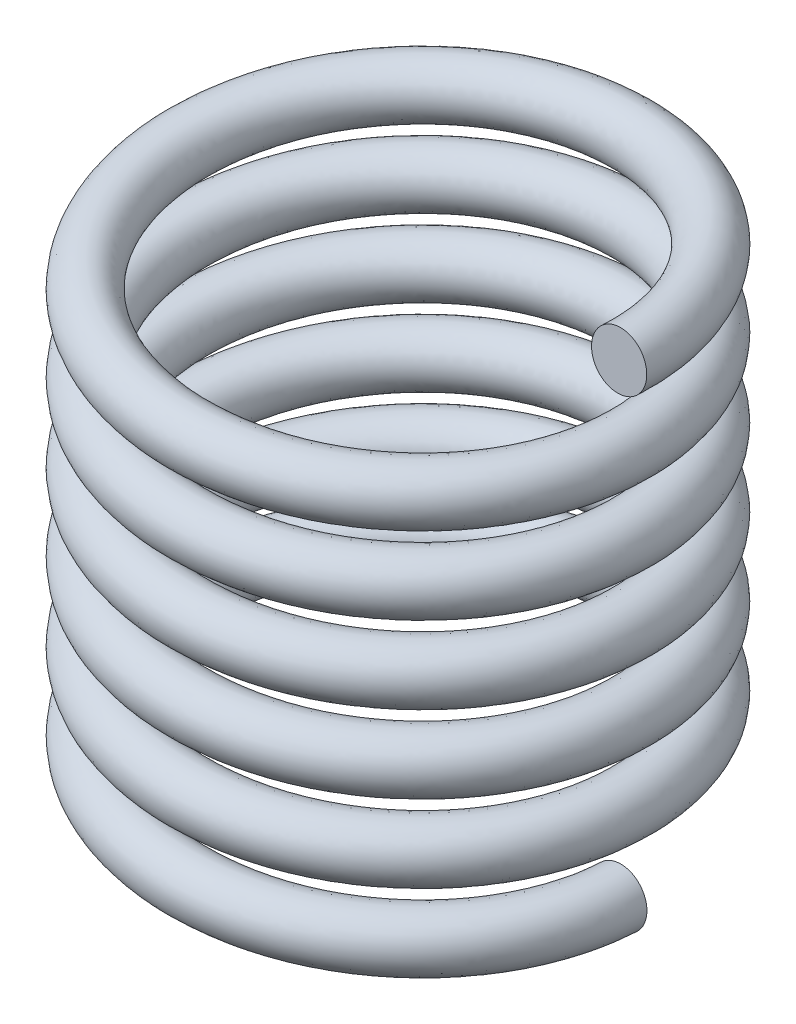
SolidWorks part; units mm, degrees
ref_plane "前视基准面" through (0, 0, 0) normal (0, 0, 1) x (1, 0, 0)
ref_plane "上视基准面" through (0, 0, 0) normal (0, 1, 0) x (1, 0, 0)
ref_plane "右视基准面" through (0, 0, 0) normal (1, 0, 0) x (0, 0, -1)
other "Configuration Table"
sketch3d "3D草图1"
  spline S0 degree 3 poles (10, 0, 0) (10.0054, 0.0972, 1.7467) (9.296, 0.2431, 4.3593) (7.1522, 0.4375, 7.1523) (5.0575, 0.5833, 8.7598) (2.6179, 0.7292, 9.7702) (0, 0.875, 10.1149) (-2.6179, 1.0208, 9.7702) (-5.0574, 1.1667, 8.7597) (-7.1523, 1.3125, 7.1523) (-8.7597, 1.4583, 5.0574) (-9.7702, 1.6042, 2.6179) (-10.1149, 1.75, 0) (-9.7702, 1.8958, -2.6179) (-8.7597, 2.0417, -5.0574) (-7.1523, 2.1875, -7.1523) (-5.0574, 2.3333, -8.7597) (-2.6179, 2.4792, -9.7702) (0, 2.625, -10.1149) (2.6179, 2.7708, -9.7702) (5.0574, 2.9167, -8.7597) (7.1523, 3.0625, -7.1523) (8.7597, 3.2083, -5.0574) (9.7702, 3.3542, -2.6179) (10.1149, 3.5, 0) (9.7702, 3.6458, 2.6179) (8.7597, 3.7917, 5.0574) (7.1523, 3.9375, 7.1523) (5.0574, 4.0833, 8.7597) (2.6179, 4.2292, 9.7702) (0, 4.375, 10.1149) (-2.6179, 4.5208, 9.7702) (-5.0574, 4.6667, 8.7597) (-7.1523, 4.8125, 7.1523) (-8.7597, 4.9583, 5.0574) (-9.7702, 5.1042, 2.6179) (-10.1149, 5.25, 0) (-9.7702, 5.3958, -2.6179) (-8.7597, 5.5417, -5.0574) (-7.1523, 5.6875, -7.1523) (-5.0574, 5.8333, -8.7597) (-2.6179, 5.9792, -9.7702) (0, 6.125, -10.1149) (2.6179, 6.2708, -9.7702) (5.0574, 6.4167, -8.7597) (7.1523, 6.5625, -7.1523) (8.7597, 6.7083, -5.0574) (9.7702, 6.8542, -2.6179) (10.1149, 7, 0) (9.7702, 7.1458, 2.6179) (8.7597, 7.2917, 5.0574) (7.1523, 7.4375, 7.1523) (5.0574, 7.5833, 8.7597) (2.6179, 7.7292, 9.7702) (0, 7.875, 10.1149) (-2.6179, 8.0208, 9.7702) (-5.0574, 8.1667, 8.7597) (-7.1523, 8.3125, 7.1523) (-8.7597, 8.4583, 5.0574) (-9.7702, 8.6042, 2.6179) (-10.1149, 8.75, 0) (-9.7702, 8.8958, -2.6179) (-8.7597, 9.0417, -5.0574) (-7.1523, 9.1875, -7.1523) (-5.0574, 9.3333, -8.7597) (-2.6179, 9.4792, -9.7702) (0, 9.625, -10.1149) (2.6179, 9.7708, -9.7702) (5.0574, 9.9167, -8.7597) (7.1523, 10.0625, -7.1523) (8.7597, 10.2083, -5.0574) (9.7702, 10.3542, -2.6179) (10.1149, 10.5, 0) (9.7702, 10.6458, 2.6179) (8.7597, 10.7917, 5.0574) (7.1523, 10.9375, 7.1523) (5.0574, 11.0833, 8.7597) (2.6179, 11.2292, 9.7702) (0, 11.375, 10.1149) (-2.6179, 11.5208, 9.7702) (-5.0574, 11.6667, 8.7597) (-7.1523, 11.8125, 7.1523) (-8.7597, 11.9583, 5.0574) (-9.7702, 12.1042, 2.6179) (-10.1149, 12.25, 0) (-9.7702, 12.3958, -2.6179) (-8.7597, 12.5417, -5.0574) (-7.1523, 12.6875, -7.1523) (-5.0574, 12.8333, -8.7597) (-2.6179, 12.9792, -9.7702) (0, 13.125, -10.1149) (2.6179, 13.2708, -9.7702) (5.0574, 13.4167, -8.7597) (7.1523, 13.5625, -7.1523) (8.7597, 13.7083, -5.0574) (9.7702, 13.8542, -2.6179) (10.1149, 14, 0) (9.7702, 14.1458, 2.6179) (8.7597, 14.2917, 5.0574) (7.1523, 14.4375, 7.1523) (5.0574, 14.5833, 8.7597) (2.6179, 14.7292, 9.7702) (0, 14.875, 10.1149) (-2.6179, 15.0208, 9.7702) (-5.0574, 15.1667, 8.7597) (-7.1523, 15.3125, 7.1523) (-8.7597, 15.4583, 5.0574) (-9.7702, 15.6042, 2.6179) (-10.1149, 15.75, 0) (-9.7702, 15.8958, -2.6179) (-8.7597, 16.0417, -5.0574) (-7.1523, 16.1875, -7.1523) (-5.0574, 16.3333, -8.7597) (-2.6179, 16.4792, -9.7702) (0, 16.625, -10.1149) (2.6179, 16.7708, -9.7702) (5.0574, 16.9167, -8.7597) (7.1523, 17.0625, -7.1523) (8.7597, 17.2083, -5.0574) (9.7702, 17.3542, -2.6179) (10.1149, 17.5, 0) (9.7702, 17.6458, 2.6179) (8.7597, 17.7917, 5.0574) (7.1523, 17.9375, 7.1523) (5.0574, 18.0833, 8.7597) (2.6179, 18.2292, 9.7702) (0, 18.375, 10.1149) (-2.6179, 18.5208, 9.7702) (-5.0574, 18.6667, 8.7597) (-7.1523, 18.8125, 7.1523) (-8.7597, 18.9583, 5.0574) (-9.7702, 19.1042, 2.6179) (-10.1149, 19.25, 0) (-9.7702, 19.3958, -2.6179) (-8.7597, 19.5417, -5.0574) (-7.1523, 19.6875, -7.1523) (-5.0574, 19.8333, -8.7597) (-2.6179, 19.9792, -9.7702) (0, 20.125, -10.1149) (2.6179, 20.2708, -9.7702) (5.0575, 20.4167, -8.7598) (7.1522, 20.5625, -7.1523) (9.296, 20.7569, -4.3593) (10.0054, 20.9028, -1.7467) (10, 21, 0) knots 0 0 0 0 0.013889 0.020833 0.027778 0.034722 0.041667 0.048611 0.055556 0.0625 0.069444 0.076389 0.083333 0.090278 0.097222 0.104167 0.111111 0.118056 0.125 0.131944 0.138889 0.145833 0.152778 0.159722 0.166667 0.173611 0.180556 0.1875 0.194444 0.201389 0.208333 0.215278 0.222222 0.229167 0.236111 0.243056 0.25 0.256944 0.263889 0.270833 0.277778 0.284722 0.291667 0.298611 0.305556 0.3125 0.319444 0.326389 0.333333 0.340278 0.347222 0.354167 0.361111 0.368056 0.375 0.381944 0.388889 0.395833 0.402778 0.409722 0.416667 0.423611 0.430556 0.4375 0.444444 0.451389 0.458333 0.465278 0.472222 0.479167 0.486111 0.493056 0.5 0.506944 0.513889 0.520833 0.527778 0.534722 0.541667 0.548611 0.555556 0.5625 0.569444 0.576389 0.583333 0.590278 0.597222 0.604167 0.611111 0.618056 0.625 0.631944 0.638889 0.645833 0.652778 0.659722 0.666667 0.673611 0.680556 0.6875 0.694444 0.701389 0.708333 0.715278 0.722222 0.729167 0.736111 0.743056 0.75 0.756944 0.763889 0.770833 0.777778 0.784722 0.791667 0.798611 0.805556 0.8125 0.819444 0.826389 0.833333 0.840278 0.847222 0.854167 0.861111 0.868056 0.875 0.881944 0.888889 0.895833 0.902778 0.909722 0.916667 0.923611 0.930556 0.9375 0.944444 0.951389 0.958333 0.965278 0.972222 0.979167 0.986111 1 1 1 1
sweep "扫描1" add path "3D草图1" parameters "D3"=2.5
